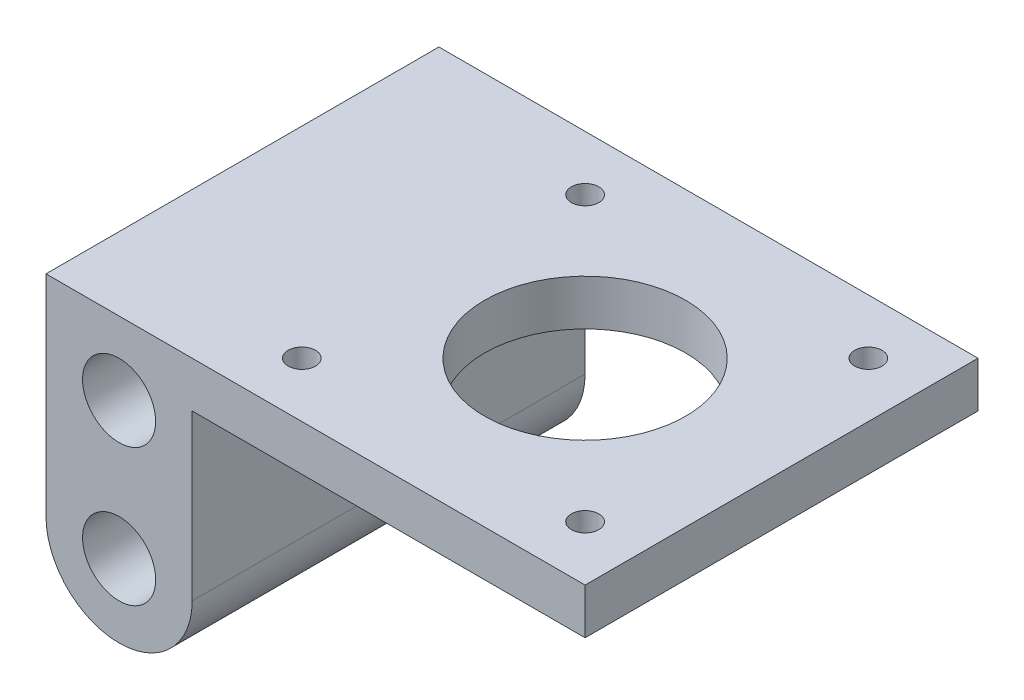
SolidWorks part; units mm, degrees
material "ABS"
ref_plane "Front Plane" through (0, 0, 0) normal (0, 0, 1) x (1, 0, 0)
ref_plane "Top Plane" through (0, 0, 0) normal (0, 1, 0) x (1, 0, 0)
ref_plane "Right Plane" through (0, 0, 0) normal (1, 0, 0) x (0, 0, -1)
sketch "Sketch1" plane through (0, 0, 0) normal (0, 0, 1) x (1, 0, 0)
  line L0 (-9.7446, 5.9304) -> (-9.7446, -17.0696)
  line L1 (6.2554, -17.0696) -> (6.2554, 0.9304)
  line L2 (-9.7446, 5.9304) -> (49.2554, 5.9304)
  line L3 (49.2554, 5.9304) -> (49.2554, 0.9304)
  line L4 (49.2554, 0.9304) -> (6.2554, 0.9304)
  circle A0 centre (-1.7446, -17.0696) radius 4
  circle A1 centre (-1.7446, -2.0696) radius 4
  arc A2 (-9.7446, -17.0696) -> (6.2554, -17.0696) centre (-1.7446, -17.0696) ccw
  dimension "D1" = 8
  dimension "D2" = 8
  dimension "D3" = 15
  dimension "D4" = 8
  dimension "D5" = 8
  dimension "D7" = 5
  dimension "D8" = 43
extrude "Boss-Extrude1" add sketch "Sketch1" against normal blind 43
sketch "Sketch2" plane through (0, 5.9304, 0) normal (0, 1, 0) x (1, 0, 0)
  line L0 (49.2554, 43) -> (49.2554, 0) construction
  line L1 (49.2554, 0) -> (-9.7446, 0) construction
  circle A0 centre (27.7554, 21.5) radius 11
  circle A1 centre (43.2554, 37) radius 1.5
  circle A2 centre (12.2554, 37) radius 1.5
  circle A3 centre (12.2554, 6) radius 1.5
  circle A4 centre (43.2554, 6) radius 1.5
  dimension "D3" = 22
  dimension "D4" = 3
  dimension "D1" = 21.5
  dimension "D2" = 21.5
  dimension "D5" = 15.5
  dimension "D6" = 15.5
  dimension "D7" = 2
  dimension "D8" = 2
extrude "Cut-Extrude1" cut sketch "Sketch2" against normal through all
equation "\"rod_diameter\"= 8"
equation "\"rod_hole_thickness\"= 4"
equation "\"rod_radius\"= \"rod_diameter\" / 2"
equation "\"platter_diameter\"= 320"
equation "\"platter_radius\"= \"platter_diameter\" / 2"
equation "\"extruder_mount_hole_spacing\"= 90"
equation "\"arm_rod_spacing\"= 40"
equation "\"top_frame_rod_spacing\"= \"arm_rod_spacing\" + 40"
equation "\"D1@Sketch1\"=\"rod_diameter\""
equation "\"D2@Sketch1\"=\"rod_diameter\""
equation "\"D3@Sketch1\"= \"motor_level_rod_spacing\""
equation "\"D1@Sketch2\" = \"D8@Sketch1\" / 2"
equation "\"D2@Sketch2\"= \"D1@Boss-Extrude1\" / 2"
equation "\"D4@Sketch1\"=\"rod_radius\"+\"rod_hole_thickness\""
equation "\"D5@Sketch1\"=\"rod_radius\"+\"rod_hole_thickness\""
equation "\"motor_level_rod_spacing\"= 15"
